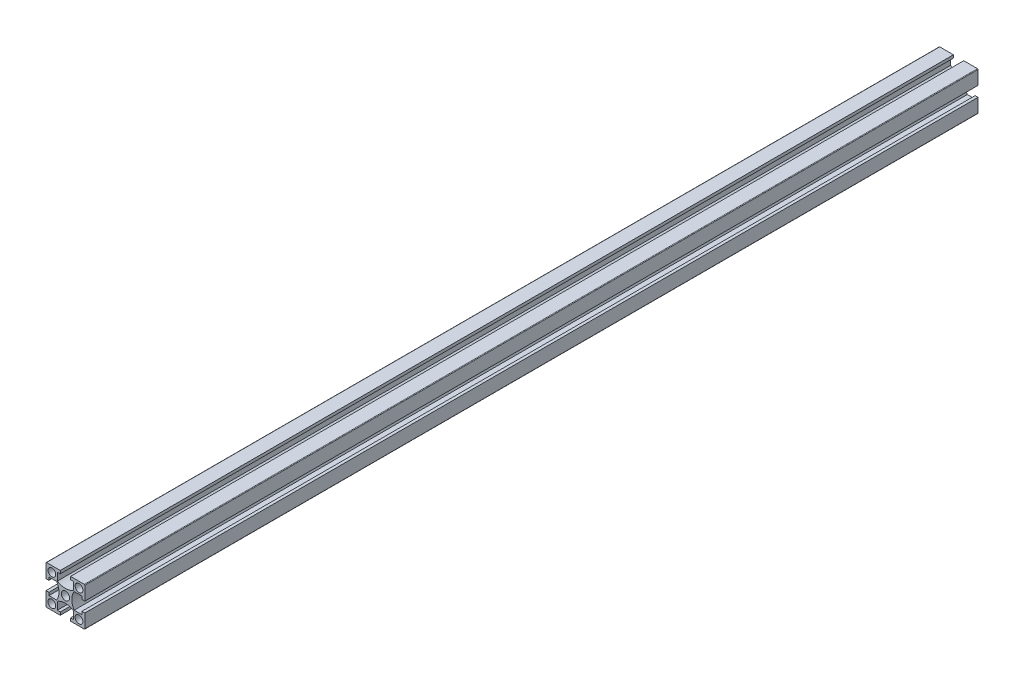
SolidWorks part; units mm, degrees
ref_plane "정면" through (0, 0, 0) normal (0, 0, 1) x (1, 0, 0)
ref_plane "윗면" through (0, 0, 0) normal (0, 1, 0) x (1, 0, 0)
ref_plane "우측면" through (0, 0, 0) normal (1, 0, 0) x (0, 0, -1)
sketch "스케치1" plane through (0, 0, 0) normal (0, 0, 1) x (1, 0, 0)
  line L0 (0, 32.0265) -> (0, -31.6588) construction
  line L1 (-10, 10) -> (-10, -10)
  line L2 (-10, 10) -> (10, 10)
  line L3 (-10, 2.65) -> (-8.5, 2.65)
  line L4 (13.6618, 0) -> (-11.6993, 0) construction
  line L5 (-8.5, 2.65) -> (-8.5, 4.15)
  line L6 (-8.5, 4.15) -> (-4.5032, 4.15)
  line L7 (-10, -2.65) -> (-8.5, -2.65)
  line L8 (-8.5, -2.65) -> (-8.5, -4.15)
  line L9 (-8.5, -4.15) -> (-4.5032, -4.15)
  line L10 (-10, -10) -> (10, -10)
  line L11 (10, 10) -> (10, -10)
  circle A0 centre (-7, 7) radius 2
  circle A1 centre (-7, -7) radius 2
  arc A2 (-4.5032, 4.15) -> (-4.5032, -4.15) centre (-11.0587, 0) cw
  circle A3 centre (0, 0) radius 2.15
  circle A4 centre (7, 7) radius 2
  circle A5 centre (7, -7) radius 2
  point P21 (-10, 0)
  point P23 (-3.3, 0)
  point P31 (0, -10)
  point P32 (0, 10)
  dimension "D3" = 4
  dimension "D9" = 6.7
  dimension "D10" = 4.3
  dimension "D11" = 7.7587
  dimension "D1" = 20
  dimension "D2" = 20
  dimension "D4" = 14
  dimension "D5" = 14
  dimension "D6" = 5.3
  dimension "D7" = 8.3
  dimension "D8" = 1.5
extrude "보스-돌출1" add sketch "스케치1" along normal blind 460 contours A0 | A4 | A3 | A5 | A1 | A2 L6 L5 L3 L1 L7 L8 L9 | L2 L11 L10 L1 region at (-6.6069, 0, 0) region at (-7, 7, 0) region at (-7, -7, 0) region at (0, 0, 0) region at (7, 7, 0) region at (7, -7, 0)
extrude "컷-돌출1" cut sketch "스케치1<3>" along normal up to next contours A2 L6 L5 L3 L1 L7 L8 L9 region at (-6.6069, 0, 0)
sketch "스케치1<3>" plane through (0, 0, 0) normal (0, 0, 1) x (1, 0, 0) same geometry as "스케치1"
pattern_circular "원형 패턴1" count 4 over 360 about axis through (0, 0, 460) along (0, 0, -1) of "컷-돌출1" reverse direction yes
fillet "필렛1" radius 0.3 4 edges at (10, -10, 230) (-10, -10, 230) (-10, 10, 230) (10, 10, 230)
